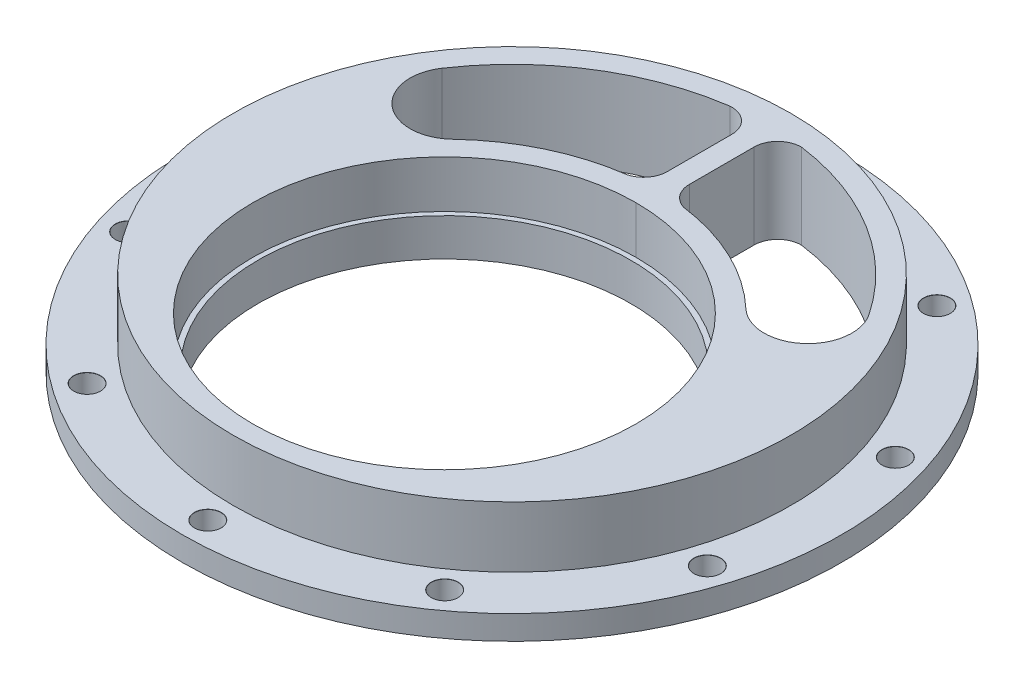
SolidWorks part; units mm, degrees
material "7075-T6, Plate (SS)"
ref_plane "X-Y Datum" through (0, 0, 0) normal (0, 0, 1) x (1, 0, 0)
ref_plane "X-Z Datum" through (0, 0, 0) normal (0, 1, 0) x (1, 0, 0)
ref_plane "Y-Z Datum" through (0, 0, 0) normal (1, 0, 0) x (0, 0, -1)
sketch "Sketch1" plane through (0, 0, 0) normal (0, 1, 0) x (1, 0, 0)
  line L0 (0, 0) -> (0, -12.7) construction
  line L1 (0, -43.0151) -> (0, 43.0151) construction
  line L2 (0, 61.9125) -> (0, 52.3875)
  circle A0 centre (0, -12.7) radius 35.052
  circle A1 centre (0, 0) radius 52.3875 construction
  circle A2 centre (0, 0) radius 57.15 construction
  circle A3 centre (0, 0) radius 61.9125
  point P12 (0, 57.15)
  dimension "D2" = 70.104
  dimension "D3" = 104.775
  dimension "D4" = 123.825
  dimension "D5" = 114.3
  dimension "D1" = 12.7
extrude "Boss-Extrude1" add sketch "Sketch1" along normal blind 4.5212 contours A3 A0 region at (-42.5405, 0, 42.5405)
sketch "Sketch3" plane through (0, 4.5212, 0) normal (0, 1, 0) x (1, 0, 0)
  circle A0 centre (0, 0) radius 52.3875 construction
  circle A1 centre (0, 0) radius 52.3875
extrude "Boss-Extrude2" add sketch "Sketch3" along normal blind 11.43
sketch "Sketch4" plane through (0, 0, 0) normal (0, -1, 0) x (1, 0, 0)
  circle A0 centre (0, 12.7) radius 35.052 construction
  circle A1 centre (0, 12.7) radius 35.052
extrude "Cut-Extrude1" cut sketch "Sketch4" against normal through all
sketch "Sketch9" plane through (0, 15.9512, 0) normal (0, 1, 0) x (1, 0, 0)
  circle A0 centre (0, -12.7) radius 35.052 construction
  circle A1 centre (0, -12.7) radius 35.052 construction
  circle A2 centre (0, -12.7) radius 36
  dimension "D1" = 72
extrude "Cut-Extrude3" cut sketch "Sketch9" against normal blind 8.89
hole_wizard "Ø5.0mm Dowel Hole1" positions "Sketch7" profile "Sketch8" hole size "Ø5.0" standard "ANSI Metric" end condition through all
sketch "Sketch7" plane through (0, 4.5212, 0) normal (0, 1, 0) x (1, 0, 0)
  point P0 (0, 57.15)
sketch "Sketch8" plane through (0, 4.5212, -57.15) normal (1, 0, 0) x (0, 0, 1)
  line L0 (0, 0) -> (0, 4.5212)
  line L1 (0, 4.5212) -> (2.5, 4.5212)
  line L2 (2.5, 4.5212) -> (2.5, 0.025)
  line L3 (2.5, 0.025) -> (2.525, 0)
  line L5 (2.525, 0) -> (0, 0)
  line L6 (-2.5, 0.025) -> (-2.525, 0) construction
  line L11 (0, -6.35) -> (0, 107.95) construction
  dimension "Thru Hole Dia." = 5
  dimension "Thru Hole Depth" = 4.5212
  dimension "Near C'Sink Dia." = 5.05
  dimension "Near C'Sink Angle" = 90
pattern_circular "CirPattern1" count 10 over 360 about axis through (0, 15.9512, 0) along (0, -1, 0) of "Ø5.0mm Dowel Hole1" reverse direction yes
ref_point "Point1"
ref_plane "Plane1" through (0, 0, 0) normal (1, 0, 0) x (0, 0, -1)
split line "Split Line1"
ref_plane "Plane2" through (0, 7.9756, 0) normal (0, 1, 0) x (1, 0, 0)
sketch "Sketch14" plane through (0, 7.9756, 0) normal (0, 1, 0) x (1, 0, 0)
  circle A0 centre (-33.2491, 22.3603) radius 8.255
ref_point "Point4"
sketch "Sketch10" plane through (0, 15.9512, 0) normal (0, 1, 0) x (1, 0, 0)
  circle A0 centre (0, 0) radius 52.3875 construction
  circle A1 centre (0, 0) radius 52.3875 construction
  circle A3 centre (-33.2491, 22.3603) radius 8.255 construction
  circle A4 centre (33.2491, 22.3603) radius 8.255 construction
  arc A7 (0, -52.764) -> (0, 27.364) centre (0, -12.7) ccw
  arc A8 (0, 27.364) -> (0, -52.764) centre (0, -12.7) ccw
  arc A9 (0, -52.764) -> (0, 27.364) centre (0, -12.7) ccw construction
  arc A10 (0, 27.364) -> (0, -52.764) centre (0, -12.7) ccw construction
  circle A29 centre (0, 0) radius 48.3235 construction
  arc A30 (-27.5687, 16.3704) -> (27.5687, 16.3704) centre (0, -12.7) cw
  arc A31 (-40.0992, 26.967) -> (40.0992, 26.967) centre (0, 0) cw
  arc A32 (-40.0992, 26.967) -> (-27.5687, 16.3704) centre (-33.2491, 22.3603) ccw
  arc A33 (27.5687, 16.3704) -> (40.0992, 26.967) centre (33.2491, 22.3603) ccw
  dimension "D3" = 16.51
  dimension "D1" = 4.064
  dimension "D2" = 4.064
extrude "Cut-Extrude5" cut sketch "Sketch10" against normal through all contours A33 A31 A32 A30
sketch "Sketch15" plane through (0, 7.9756, 0) normal (0, 1, 0) x (1, 0, 0)
  line L1 (-2.1171, 31.2835) -> (-2.1171, 43.3958)
  line L4 (2.032, 31.291) -> (2.032, 43.4389)
  line L6 (-2.1764, 48.3235) -> (-2.1667, 48.2749) construction
  line L8 (2.1667, 48.2749) -> (2.1764, 48.3235) construction
  arc A0 (27.5687, 16.3704) -> (-27.5687, 16.3704) centre (0, -12.7) ccw construction
  arc A1 (27.5687, 16.3704) -> (-27.5687, 16.3704) centre (0, -12.7) ccw construction
  arc A2 (40.0992, 26.967) -> (-40.0992, 26.967) centre (0, 0) ccw construction
  arc A3 (-2.1171, 43.3958) -> (-6.9062, 47.8275) centre (-6.5621, 43.3958) ccw
  arc A4 (40.0992, 26.967) -> (-40.0992, 26.967) centre (0, 0) ccw construction
  arc A5 (6.5037, 47.8838) -> (2.032, 43.4389) centre (6.477, 43.4389) ccw
  arc A7 (-2.1171, 31.2835) -> (-5.362, 27.0036) centre (-6.5621, 31.2835) cw
  arc A9 (2.032, 31.291) -> (5.2509, 27.0184) centre (6.477, 31.291) ccw
  arc A10 (-6.9062, 47.8275) -> (6.5037, 47.8838) centre (0, 0) cw
  arc A11 (-5.362, 27.0036) -> (5.2509, 27.0184) centre (0, -12.7) cw
  point P9 (0, 37.4715)
  dimension "D1" = 4.445
  dimension "D2" = 2.1171
  dimension "D3" = 4.445
  dimension "D4" = 2.032
  dimension "D5" = 43.4389
  dimension "D6" = 31.2835
  dimension "D7" = 2.1171
  dimension "D8" = 12.148
  dimension "D9" = 12.1123
extrude "Boss-Extrude3" add sketch "Sketch15" along normal up to surface and the other way up to surface contours A9 L4 A5 A10 A3 L1 A7 A11 region at (-0.0494, 7.9756, -38.2136) up to face at (0, 15.9512, -26.9504) other way up to face at (0, 0, -26.9504)
sketch "Sketch20" plane through (0, 4.5212, 0) normal (0, 1, 0) x (1, 0, 0)
  circle A0 centre (0, 0) radius 52.3875
  circle A2 centre (0, 0) radius 66.6087
sketch "Sketch25" plane through (0, 15.9512, 0) normal (0, 1, 0) x (1, 0, 0)
  line L6 (-4.6571, 31.2835) -> (-4.6571, 43.3958)
  line L7 (-4.6571, 31.2835) -> (-4.6571, 43.3958)
  line L12 (4.572, 43.4389) -> (4.572, 31.291)
  line L13 (4.572, 43.4389) -> (4.572, 31.291)
  circle A1 centre (-51.685, -7.6867) radius 0.134
  circle A2 centre (49.3335, -18.9489) radius 0.46
  arc A3 (48.8818, -18.8622) -> (48.9404, -18.71) centre (-0.2183, 0.1504) ccw
  arc A4 (48.8818, -18.8622) -> (48.9404, -18.71) centre (-0.2183, 0.1504) ccw
  arc A45 (-4.6571, 43.3958) -> (-6.6423, 45.2991) centre (-6.5621, 43.3958) ccw
  arc A46 (-5.9167, 29.4912) -> (-4.6571, 31.2835) centre (-6.5621, 31.2835) ccw
  arc A47 (-5.9167, 29.4912) -> (-29.3165, 18.2135) centre (0, -12.7) ccw
  arc A48 (-37.9914, 25.5495) -> (-29.3165, 18.2135) centre (-33.2491, 22.3603) ccw
  arc A49 (-6.6423, 45.2991) -> (-37.9914, 25.5495) centre (0, 0) ccw
  arc A50 (-4.6571, 43.3958) -> (-6.6423, 45.2991) centre (-6.5621, 43.3958) ccw
  arc A51 (-5.9167, 29.4912) -> (-4.6571, 31.2835) centre (-6.5621, 31.2835) ccw
  arc A52 (-5.9167, 29.4912) -> (-29.3165, 18.2135) centre (0, -12.7) ccw
  arc A53 (-37.9914, 25.5495) -> (-29.3165, 18.2135) centre (-33.2491, 22.3603) ccw
  arc A54 (-6.6423, 45.2991) -> (-37.9914, 25.5495) centre (0, 0) ccw
  circle A68 centre (-0.2183, 0.1504) radius 52.1224
  circle A69 centre (0, -12.7) radius 32.512
  circle A70 centre (0, -12.7) radius 32.512
  arc A72 (29.3165, 18.2135) -> (37.9914, 25.5495) centre (33.2491, 22.3603) ccw
  arc A73 (4.572, 31.291) -> (5.8124, 29.5056) centre (6.477, 31.291) ccw
  arc A74 (29.3165, 18.2135) -> (5.8124, 29.5056) centre (0, -12.7) ccw
  arc A75 (37.9914, 25.5495) -> (6.3564, 45.3401) centre (0, 0) ccw
  arc A76 (6.3564, 45.3401) -> (4.572, 43.4389) centre (6.477, 43.4389) ccw
  arc A77 (29.3165, 18.2135) -> (37.9914, 25.5495) centre (33.2491, 22.3603) ccw
  arc A78 (4.572, 31.291) -> (5.8124, 29.5056) centre (6.477, 31.291) ccw
  arc A79 (29.3165, 18.2135) -> (5.8124, 29.5056) centre (0, -12.7) ccw
  arc A80 (37.9914, 25.5495) -> (6.3564, 45.3401) centre (0, 0) ccw
  arc A81 (6.3564, 45.3401) -> (4.572, 43.4389) centre (6.477, 43.4389) ccw
  arc M3 (27.5687, 16.3704) -> (5.2509, 27.0184) centre (0, -12.7) ccw
  arc M4 (5.2509, 27.0184) -> (2.032, 31.291) centre (6.477, 31.291) cw
  line M5 (2.032, 31.291) -> (2.032, 43.4389)
  arc M6 (2.032, 43.4389) -> (6.5037, 47.8838) centre (6.477, 43.4389) cw
  arc M7 (6.5037, 47.8838) -> (40.0992, 26.967) centre (0, 0) cw
  arc M8 (40.0992, 26.967) -> (27.5687, 16.3704) centre (33.2491, 22.3603) cw
  arc M9 (-5.362, 27.0036) -> (-27.5687, 16.3704) centre (0, -12.7) ccw
  arc M10 (-27.5687, 16.3704) -> (-40.0992, 26.967) centre (-33.2491, 22.3603) cw
  arc M11 (-40.0992, 26.967) -> (-6.9062, 47.8275) centre (0, 0) cw
  arc M12 (-6.9062, 47.8275) -> (-2.1171, 43.3958) centre (-6.5621, 43.3958) cw
  line M13 (-2.1171, 43.3958) -> (-2.1171, 31.2835)
  arc M14 (-2.1171, 31.2835) -> (-5.362, 27.0036) centre (-6.5621, 31.2835) cw
  arc M15 (0, 23.3) -> (0, -48.7) centre (0, -12.7) cw
  arc M16 (0, -48.7) -> (0, 23.3) centre (0, -12.7) cw
  dimension "D1" = 2.54
  dimension "D2" = 2.54
  dimension "D3" = 2.54
extrude "Boss-Extrude5" [suppressed] add sketch "Sketch25" along normal blind 1.27 contours A54 A50 L7 A51 A52 A53 M9 M14 M13 M12 M11 M10 | A70 M15 M16 | A68 A1 M16 M15 M14 M9 M10 M11 M12 M13 M8 M3 M4 M5 M6 M7 | A81 A80 A77 A79 A78 L13 M3 M8 M7 M6 M5 M4
sketch "Sketch26" plane through (0, 4.5212, 0) normal (0, 1, 0) x (1, 0, 0)
  circle A2 centre (0, 0) radius 52.3875
  arc A3 (-46.0336, 25.0072) -> (-51.9408, 6.8266) centre (-49.7593, 16.1678) ccw
  arc A4 (-22.5431, 47.2891) -> (-38.0084, 36.0529) centre (-30.7529, 42.3278) ccw
  arc A5 (9.5581, 51.5082) -> (-9.5581, 51.5082) centre (0, 52.32) ccw
  arc A6 (38.0084, 36.0529) -> (22.5431, 47.2891) centre (30.7529, 42.3278) ccw
  arc A7 (51.9408, 6.8266) -> (46.0336, 25.0072) centre (49.7593, 16.1678) ccw
  arc A8 (46.0336, -25.0072) -> (51.9408, -6.8266) centre (49.7593, -16.1678) ccw
  arc A9 (22.5431, -47.2891) -> (38.0084, -36.0529) centre (30.7529, -42.3278) ccw
  arc A10 (-9.5581, -51.5082) -> (9.5581, -51.5082) centre (0, -52.32) ccw
  arc A11 (-38.0084, -36.0529) -> (-22.5431, -47.2891) centre (-30.7529, -42.3278) ccw
  arc A12 (-51.9408, -6.8266) -> (-46.0336, -25.0072) centre (-49.7593, -16.1678) ccw
  point P3 (-49.7593, 16.1678)
  point P37 (0, 0)
  circle M14 centre (0, 0) radius 61.9125
  dimension "D1" = 10
extrude "Cut-Extrude6" [suppressed] cut sketch "Sketch26" against normal through all both and the other way through all contours A4 A3 A2 M14 | A5 A4 A2 M14 | A6 A5 A2 M14 | A7 A6 A2 M14 | A8 A7 A2 M14 | A9 A8 A2 M14 | A10 A9 A2 M14 | A11 A10 A2 M14 | A12 A11 A2 M14 | A12 A2 A3 M14
fillet "Fillet1" [suppressed] radius 7.62
